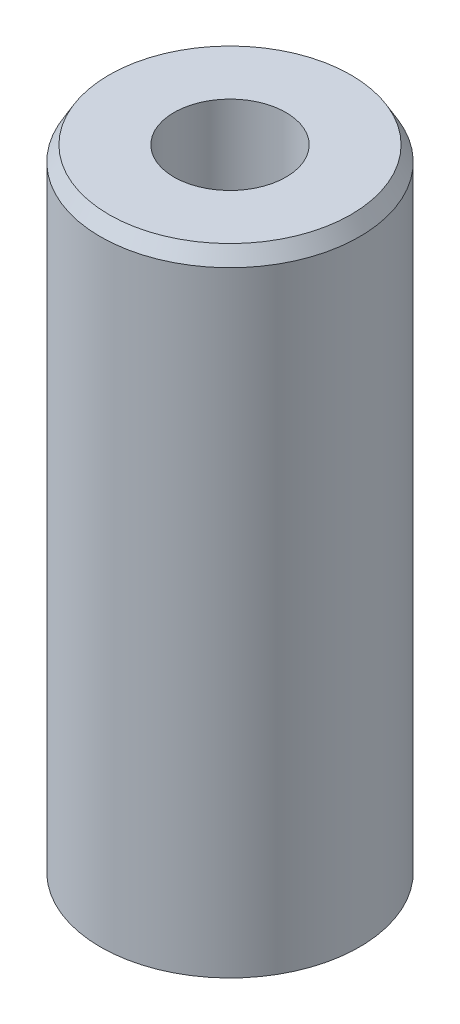
SolidWorks part; units mm, degrees
ref_plane "Front Plane" through (0, 0, 0) normal (0, 0, 1) x (1, 0, 0)
ref_plane "Top Plane" through (0, 0, 0) normal (0, 1, 0) x (1, 0, 0)
ref_plane "Right Plane" through (0, 0, 0) normal (1, 0, 0) x (0, 0, -1)
sketch "Sketch1" plane through (0, 0, 0) normal (0, 1, 0) x (1, 0, 0)
  circle A0 centre (0, 0) radius 17.5
  dimension "SHAFT_OD" = 35
extrude "Boss-Extrude1" add sketch "Sketch1" along normal blind 86.2438
sketch "Sketch2" plane through (0, 0, 0) normal (0, 1, 0) x (1, 0, 0)
  circle A0 centre (0, 0) radius 7.5648
  dimension "BORE_D" = 15.1295
extrude "Cut-Extrude1" cut sketch "Sketch2" along normal through all
chamfer "Chamfer1" distance 2.0082 angle 30 2 edges at (0, 86.2438, 17.5) (0, 0, 17.5) first distance on face at (0, 86.2438, 17.5) first distance on face at (0, 0, 7.5648)
